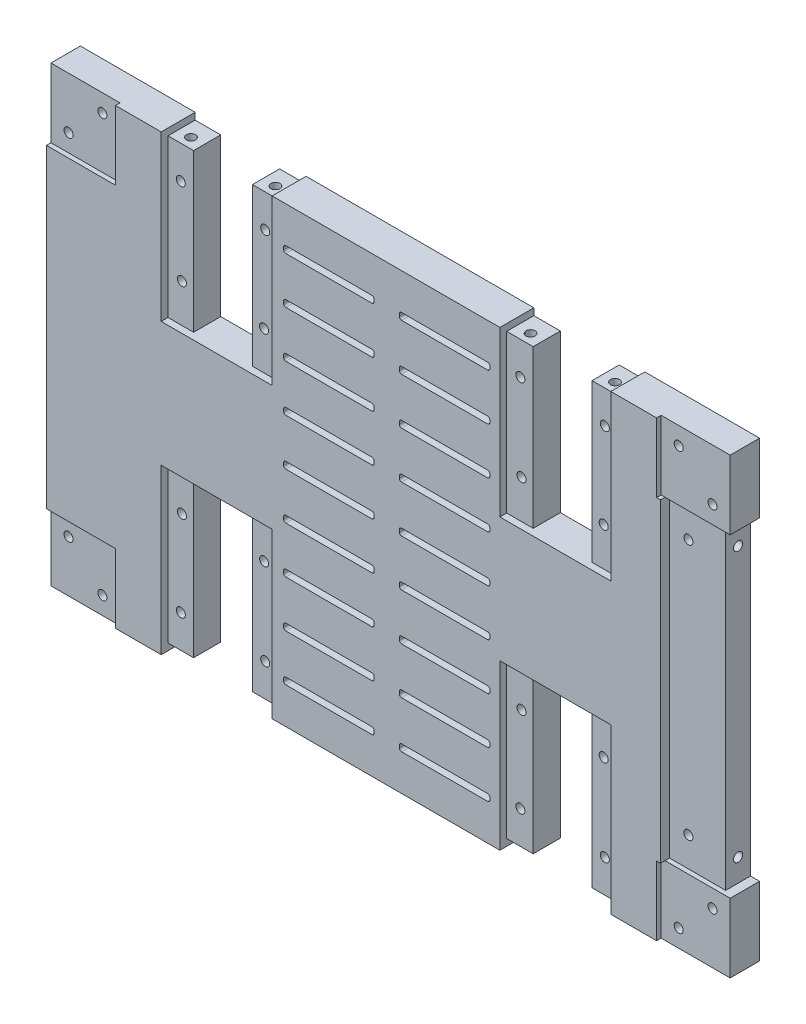
SolidWorks part; units mm, degrees
ref_plane "Alzado" through (0, 0, 0) normal (0, 0, 1) x (1, 0, 0)
ref_plane "Planta" through (0, 0, 0) normal (0, 1, 0) x (1, 0, 0)
ref_plane "Vista lateral" through (0, 0, 0) normal (1, 0, 0) x (0, 0, -1)
sketch "Croquis1" plane through (0, 0, 0) normal (0, 0, 1) x (1, 0, 0)
  line L1 (150, 100) -> (-150, 100)
  line L2 (150, 100) -> (150, -100)
  line L3 (150, -100) -> (-150, -100)
  line L4 (-150, 100) -> (-150, -100)
  line L5 (150, 100) -> (-150, -100) construction
  line L6 (150, -100) -> (-150, 100) construction
  point P0 (0, 0)
  dimension "D1" = 300
  dimension "D2" = 200
extrude "Saliente-Extruir1" add sketch "Croquis1" along normal blind 15
sketch "Croquis2" plane through (0, 0, 15) normal (0, 0, 1) x (1, 0, 0)
  line L0 (0, 0) -> (0, 100) construction
  line L1 (-150, 100) -> (-119.5, 100)
  line L2 (-150, 100) -> (-150, 69.5)
  line L3 (-150, 69.5) -> (-119.5, 69.5)
  line L4 (-119.5, 100) -> (-119.5, 69.5)
  line L5 (150, 100) -> (-150, 100) construction
  line L6 (0, 0) -> (150, 0) construction
  line L7 (150, -100) -> (150, 100) construction
  line L8 (150, 69.5) -> (119.5, 69.5)
  line L9 (119.5, 100) -> (119.5, 69.5)
  line L10 (150, 100) -> (119.5, 100)
  line L11 (150, 100) -> (150, 69.5)
  line L12 (150, -100) -> (150, -69.5)
  line L13 (150, -100) -> (119.5, -100)
  line L14 (119.5, -100) -> (119.5, -69.5)
  line L15 (150, -69.5) -> (119.5, -69.5)
  line L16 (-150, -69.5) -> (-119.5, -69.5)
  line L17 (-119.5, -100) -> (-119.5, -69.5)
  line L18 (-150, -100) -> (-119.5, -100)
  line L19 (-150, -100) -> (-150, -69.5)
  dimension "D1" = 30.5
extrude "Huecos columna" cut sketch "Croquis2" against normal blind 2
sketch "Croquis3" plane through (0, 0, 15) normal (0, 0, 1) x (1, 0, 0)
  line L0 (-119.5, -100) -> (119.5, -100) construction
  line L2 (-88, -97) -> (-88, -27.5)
  line L3 (-88, -27.5) -> (-62, -27.5)
  line L4 (-62, -97) -> (-62, -27.5)
  line L5 (0, 0) -> (0, -100) construction
  line L6 (0, 0) -> (-150, 0) construction
  line L7 (-150, 69.5) -> (-150, -69.5) construction
  line L8 (-88, -58.2044) -> (-150, -58.2044) construction
  line L9 (-62, -60.8904) -> (0, -60.8904) construction
  line L10 (88, -27.5) -> (62, -27.5)
  line L11 (62, -97) -> (62, -27.5)
  line L13 (88, -97) -> (88, -27.5)
  line L14 (88, 97) -> (88, 27.5)
  line L16 (62, 97) -> (62, 27.5)
  line L17 (88, 27.5) -> (62, 27.5)
  line L18 (-88, 27.5) -> (-62, 27.5)
  line L19 (-62, 97) -> (-62, 27.5)
  line L21 (-88, 97) -> (-88, 27.5)
  line L22 (-99.2954, -100) -> (-50.2954, -100)
  line L24 (-99.2954, -100) -> (-99.2954, -97)
  line L25 (-99.2954, -97) -> (-88, -97)
  line L26 (-50.2954, -100) -> (-50.2954, -97)
  line L27 (99.2954, -100) -> (50.2954, -100)
  line L28 (50.2954, -100) -> (50.2954, -97)
  line L29 (99.2954, -97) -> (88, -97)
  line L30 (99.2954, -100) -> (99.2954, -97)
  line L31 (99.2954, 100) -> (99.2954, 97)
  line L32 (99.2954, 97) -> (88, 97)
  line L33 (50.2954, 100) -> (50.2954, 97)
  line L34 (99.2954, 100) -> (50.2954, 100)
  line L35 (-99.2954, 100) -> (-50.2954, 100)
  line L36 (-50.2954, 100) -> (-50.2954, 97)
  line L37 (-99.2954, 97) -> (-88, 97)
  line L38 (-99.2954, 100) -> (-99.2954, 97)
  line L39 (-62, -97) -> (-50.2954, -97)
  line L40 (62, -97) -> (50.2954, -97)
  line L41 (62, 97) -> (50.2954, 97)
  line L42 (-62, 97) -> (-50.2954, 97)
  point P28 (-75, -100)
  point P36 (-74.7954, -100)
  dimension "D1" = 26
  dimension "D2" = 49
  dimension "D3" = 3
  dimension "D4" = 69.5
extrude "huecos  motor" cut sketch "Croquis3" against normal through all
sketch "Croquis4" plane through (0, -97, 0) normal (0, -1, 0) x (1, 0, 0)
  line L0 (-99.2954, 15) -> (-88, 0) construction
  line L1 (-88, 0) -> (-88, 15) construction
  line L2 (-88, 15) -> (-99.2954, 0) construction
  line L3 (0, 0) -> (0, 15) construction
  line L4 (-50.2954, 15) -> (50.2954, 15) construction
  line L5 (-75, 15) -> (-75, 0) construction
  line L6 (-62, 15) -> (-88, 15) construction
  line L7 (-62, 0) -> (-88, 0) construction
  circle A0 centre (-93.6477, 7.5) radius 2
  circle A1 centre (-56.3523, 7.5) radius 2
  circle A2 centre (56.3523, 7.5) radius 2
  circle A3 centre (93.6477, 7.5) radius 2
extrude "side_screws 1" cut sketch "Croquis4" against normal blind 15
sketch "Croquis5" plane through (0, 97, 0) normal (0, 1, 0) x (1, 0, 0)
  line L0 (-99.2954, 0) -> (-88, -15) construction
  line L1 (-88, -15) -> (-88, 0) construction
  line L2 (-88, 0) -> (-99.2954, -15) construction
  line L3 (-75, 0) -> (-75, -15) construction
  line L4 (-88, 0) -> (-62, 0) construction
  line L5 (-88, -15) -> (-62, -15) construction
  line L6 (0, 0) -> (0, -15) construction
  line L7 (50.2954, -15) -> (-50.2954, -15) construction
  circle A0 centre (-93.6477, -7.5) radius 2
  circle A1 centre (-56.3523, -7.5) radius 2
  circle A2 centre (56.3523, -7.5) radius 2
  circle A3 centre (93.6477, -7.5) radius 2
extrude "side screws 2" cut sketch "Croquis5" against normal blind 15
sketch "Croquis7" plane through (0, 0, 15) normal (0, 0, 1) x (1, 0, 0)
  line L0 (-150, -69.5) -> (-119.5, -100) construction
  line L1 (-150, -100) -> (-119.5, -69.5) construction
  line L2 (-150, 0) -> (0, 0) construction
  line L3 (-150, 69.5) -> (-150, -69.5) construction
  line L4 (0, 0) -> (0, -100) construction
  line L5 (-50.2954, -100) -> (50.2954, -100) construction
  line L6 (6.8759, 84) -> (44.8759, 84)
  line L7 (-44.236, 81) -> (-6.236, 81)
  line L8 (-45.236, 82) -> (-45.236, 83)
  line L9 (-44.236, 84) -> (-6.236, 84)
  line L10 (-5.236, 82) -> (-5.236, 83)
  line L11 (-45.236, 81) -> (-5.236, 84) construction
  line L12 (-45.236, 84) -> (-5.236, 81) construction
  line L13 (6.8759, 81) -> (44.8759, 81)
  line L14 (5.8759, 82) -> (5.8759, 83)
  line L15 (45.8759, 82) -> (45.8759, 83)
  line L16 (6.8759, 63.375) -> (44.8759, 63.375)
  line L17 (6.8759, 60.375) -> (44.8759, 60.375)
  line L18 (5.8759, 61.375) -> (5.8759, 62.375)
  line L19 (45.8759, 61.375) -> (45.8759, 62.375)
  line L20 (6.8759, 42.75) -> (44.8759, 42.75)
  line L21 (6.8759, 39.75) -> (44.8759, 39.75)
  line L22 (5.8759, 40.75) -> (5.8759, 41.75)
  line L23 (45.8759, 40.75) -> (45.8759, 41.75)
  line L24 (6.8759, 22.125) -> (44.8759, 22.125)
  line L25 (6.8759, 19.125) -> (44.8759, 19.125)
  line L26 (5.8759, 20.125) -> (5.8759, 21.125)
  line L27 (45.8759, 20.125) -> (45.8759, 21.125)
  line L28 (6.8759, 1.5) -> (44.8759, 1.5)
  line L29 (6.8759, -1.5) -> (44.8759, -1.5)
  line L30 (5.8759, -0.5) -> (5.8759, 0.5)
  line L31 (45.8759, -0.5) -> (45.8759, 0.5)
  line L32 (6.8759, -19.125) -> (44.8759, -19.125)
  line L33 (6.8759, -22.125) -> (44.8759, -22.125)
  line L34 (5.8759, -21.125) -> (5.8759, -20.125)
  line L35 (45.8759, -21.125) -> (45.8759, -20.125)
  line L36 (6.8759, -39.75) -> (44.8759, -39.75)
  line L37 (6.8759, -42.75) -> (44.8759, -42.75)
  line L38 (5.8759, -41.75) -> (5.8759, -40.75)
  line L39 (45.8759, -41.75) -> (45.8759, -40.75)
  line L40 (6.8759, -60.375) -> (44.8759, -60.375)
  line L41 (6.8759, -63.375) -> (44.8759, -63.375)
  line L42 (5.8759, -62.375) -> (5.8759, -61.375)
  line L43 (45.8759, -62.375) -> (45.8759, -61.375)
  line L44 (6.8759, -81) -> (44.8759, -81)
  line L45 (6.8759, -84) -> (44.8759, -84)
  line L46 (5.8759, -83) -> (5.8759, -82)
  line L47 (45.8759, -83) -> (45.8759, -82)
  line L48 (-44.236, 63.375) -> (-6.236, 63.375)
  line L49 (-44.236, 60.375) -> (-6.236, 60.375)
  line L50 (-45.236, 61.375) -> (-45.236, 62.375)
  line L51 (-5.236, 61.375) -> (-5.236, 62.375)
  line L52 (-44.236, 42.75) -> (-6.236, 42.75)
  line L53 (-44.236, 39.75) -> (-6.236, 39.75)
  line L54 (-45.236, 40.75) -> (-45.236, 41.75)
  line L55 (-5.236, 40.75) -> (-5.236, 41.75)
  line L56 (-44.236, 22.125) -> (-6.236, 22.125)
  line L57 (-44.236, 19.125) -> (-6.236, 19.125)
  line L58 (-45.236, 20.125) -> (-45.236, 21.125)
  line L59 (-5.236, 20.125) -> (-5.236, 21.125)
  line L60 (-44.236, 1.5) -> (-6.236, 1.5)
  line L61 (-44.236, -1.5) -> (-6.236, -1.5)
  line L62 (-45.236, -0.5) -> (-45.236, 0.5)
  line L63 (-5.236, -0.5) -> (-5.236, 0.5)
  line L64 (-44.236, -19.125) -> (-6.236, -19.125)
  line L65 (-44.236, -22.125) -> (-6.236, -22.125)
  line L66 (-45.236, -21.125) -> (-45.236, -20.125)
  line L67 (-5.236, -21.125) -> (-5.236, -20.125)
  line L68 (-44.236, -39.75) -> (-6.236, -39.75)
  line L69 (-44.236, -42.75) -> (-6.236, -42.75)
  line L70 (-45.236, -41.75) -> (-45.236, -40.75)
  line L71 (-5.236, -41.75) -> (-5.236, -40.75)
  line L72 (-44.236, -60.375) -> (-6.236, -60.375)
  line L73 (-44.236, -63.375) -> (-6.236, -63.375)
  line L74 (-45.236, -62.375) -> (-45.236, -61.375)
  line L75 (-5.236, -62.375) -> (-5.236, -61.375)
  line L76 (-44.236, -81) -> (-6.236, -81)
  line L77 (-44.236, -84) -> (-6.236, -84)
  line L78 (-45.236, -83) -> (-45.236, -82)
  line L79 (-5.236, -83) -> (-5.236, -82)
  line L80 (39.4634, 84) -> (39.4634, 100) construction
  line L81 (50.2954, 100) -> (-50.2954, 100) construction
  line L82 (-93.6477, -97) -> (-93.6477, -82.5) construction
  line L83 (25.8759, -84) -> (25.8759, -100) construction
  line L84 (-45.236, 82.5) -> (-56.3523, 82.5) construction
  line L85 (-5.236, 82.8086) -> (5.8759, 82.5) construction
  line L87 (45.8759, 82.5) -> (62, 82.5) construction
  line L88 (62, 97) -> (62, 27.5) construction
  line L89 (-88, -97) -> (-99.2954, -97) construction
  line L90 (-75, -27.5) -> (-75, -100) construction
  line L91 (-62, -27.5) -> (-88, -27.5) construction
  line L92 (-56.3523, -97) -> (-56.3523, -82.5) construction
  line L93 (56.3523, -97) -> (56.3523, -82.5) construction
  line L94 (93.6477, -97) -> (93.6477, -82.5) construction
  line L95 (93.6477, 97) -> (93.6477, 82.5) construction
  line L96 (56.3523, 97) -> (56.3523, 82.5) construction
  line L97 (-56.3523, 97) -> (-56.3523, 82.5) construction
  line L98 (-93.6477, 97) -> (-93.6477, 82.5) construction
  circle A0 centre (-127.2782, -92.2218) radius 2
  circle A1 centre (-142.2218, -77.2782) radius 2
  circle A2 centre (-127.2782, 92.2218) radius 2
  circle A3 centre (-142.2218, 77.2782) radius 2
  circle A4 centre (127.2782, -92.2218) radius 2
  circle A5 centre (142.2218, -77.2782) radius 2
  circle A6 centre (127.2782, 92.2218) radius 2
  circle A7 centre (142.2218, 77.2782) radius 2
  arc A8 (-5.236, 82) -> (-6.236, 81) centre (-6.236, 82) cw
  arc A9 (-5.236, 83) -> (-6.236, 84) centre (-6.236, 83) ccw
  arc A10 (-44.236, 81) -> (-45.236, 82) centre (-44.236, 82) cw
  arc A11 (-45.236, 83) -> (-44.236, 84) centre (-44.236, 83) cw
  arc A12 (5.8759, 83) -> (6.8759, 84) centre (6.8759, 83) cw
  arc A13 (6.8759, 81) -> (5.8759, 82) centre (6.8759, 82) cw
  arc A14 (45.8759, 83) -> (44.8759, 84) centre (44.8759, 83) ccw
  arc A15 (45.8759, 82) -> (44.8759, 81) centre (44.8759, 82) cw
  arc A16 (5.8759, 62.375) -> (6.8759, 63.375) centre (6.8759, 62.375) cw
  arc A17 (6.8759, 60.375) -> (5.8759, 61.375) centre (6.8759, 61.375) cw
  arc A18 (45.8759, 62.375) -> (44.8759, 63.375) centre (44.8759, 62.375) ccw
  arc A19 (45.8759, 61.375) -> (44.8759, 60.375) centre (44.8759, 61.375) cw
  arc A20 (5.8759, 41.75) -> (6.8759, 42.75) centre (6.8759, 41.75) cw
  arc A21 (6.8759, 39.75) -> (5.8759, 40.75) centre (6.8759, 40.75) cw
  arc A22 (45.8759, 41.75) -> (44.8759, 42.75) centre (44.8759, 41.75) ccw
  arc A23 (45.8759, 40.75) -> (44.8759, 39.75) centre (44.8759, 40.75) cw
  arc A24 (5.8759, 21.125) -> (6.8759, 22.125) centre (6.8759, 21.125) cw
  arc A25 (6.8759, 19.125) -> (5.8759, 20.125) centre (6.8759, 20.125) cw
  arc A26 (45.8759, 21.125) -> (44.8759, 22.125) centre (44.8759, 21.125) ccw
  arc A27 (45.8759, 20.125) -> (44.8759, 19.125) centre (44.8759, 20.125) cw
  arc A28 (5.8759, 0.5) -> (6.8759, 1.5) centre (6.8759, 0.5) cw
  arc A29 (6.8759, -1.5) -> (5.8759, -0.5) centre (6.8759, -0.5) cw
  arc A30 (45.8759, 0.5) -> (44.8759, 1.5) centre (44.8759, 0.5) ccw
  arc A31 (45.8759, -0.5) -> (44.8759, -1.5) centre (44.8759, -0.5) cw
  arc A32 (5.8759, -20.125) -> (6.8759, -19.125) centre (6.8759, -20.125) cw
  arc A33 (6.8759, -22.125) -> (5.8759, -21.125) centre (6.8759, -21.125) cw
  arc A34 (45.8759, -20.125) -> (44.8759, -19.125) centre (44.8759, -20.125) ccw
  arc A35 (45.8759, -21.125) -> (44.8759, -22.125) centre (44.8759, -21.125) cw
  arc A36 (5.8759, -40.75) -> (6.8759, -39.75) centre (6.8759, -40.75) cw
  arc A37 (6.8759, -42.75) -> (5.8759, -41.75) centre (6.8759, -41.75) cw
  arc A38 (45.8759, -40.75) -> (44.8759, -39.75) centre (44.8759, -40.75) ccw
  arc A39 (45.8759, -41.75) -> (44.8759, -42.75) centre (44.8759, -41.75) cw
  arc A40 (5.8759, -61.375) -> (6.8759, -60.375) centre (6.8759, -61.375) cw
  arc A41 (6.8759, -63.375) -> (5.8759, -62.375) centre (6.8759, -62.375) cw
  arc A42 (45.8759, -61.375) -> (44.8759, -60.375) centre (44.8759, -61.375) ccw
  arc A43 (45.8759, -62.375) -> (44.8759, -63.375) centre (44.8759, -62.375) cw
  arc A44 (5.8759, -82) -> (6.8759, -81) centre (6.8759, -82) cw
  arc A45 (6.8759, -84) -> (5.8759, -83) centre (6.8759, -83) cw
  arc A46 (45.8759, -82) -> (44.8759, -81) centre (44.8759, -82) ccw
  arc A47 (45.8759, -83) -> (44.8759, -84) centre (44.8759, -83) cw
  arc A48 (-45.236, 62.375) -> (-44.236, 63.375) centre (-44.236, 62.375) cw
  arc A49 (-44.236, 60.375) -> (-45.236, 61.375) centre (-44.236, 61.375) cw
  arc A50 (-5.236, 62.375) -> (-6.236, 63.375) centre (-6.236, 62.375) ccw
  arc A51 (-5.236, 61.375) -> (-6.236, 60.375) centre (-6.236, 61.375) cw
  arc A52 (-45.236, 41.75) -> (-44.236, 42.75) centre (-44.236, 41.75) cw
  arc A53 (-44.236, 39.75) -> (-45.236, 40.75) centre (-44.236, 40.75) cw
  arc A54 (-5.236, 41.75) -> (-6.236, 42.75) centre (-6.236, 41.75) ccw
  arc A55 (-5.236, 40.75) -> (-6.236, 39.75) centre (-6.236, 40.75) cw
  arc A56 (-45.236, 21.125) -> (-44.236, 22.125) centre (-44.236, 21.125) cw
  arc A57 (-44.236, 19.125) -> (-45.236, 20.125) centre (-44.236, 20.125) cw
  arc A58 (-5.236, 21.125) -> (-6.236, 22.125) centre (-6.236, 21.125) ccw
  arc A59 (-5.236, 20.125) -> (-6.236, 19.125) centre (-6.236, 20.125) cw
  arc A60 (-45.236, 0.5) -> (-44.236, 1.5) centre (-44.236, 0.5) cw
  arc A61 (-44.236, -1.5) -> (-45.236, -0.5) centre (-44.236, -0.5) cw
  arc A62 (-5.236, 0.5) -> (-6.236, 1.5) centre (-6.236, 0.5) ccw
  arc A63 (-5.236, -0.5) -> (-6.236, -1.5) centre (-6.236, -0.5) cw
  arc A64 (-45.236, -20.125) -> (-44.236, -19.125) centre (-44.236, -20.125) cw
  arc A65 (-44.236, -22.125) -> (-45.236, -21.125) centre (-44.236, -21.125) cw
  arc A66 (-5.236, -20.125) -> (-6.236, -19.125) centre (-6.236, -20.125) ccw
  arc A67 (-5.236, -21.125) -> (-6.236, -22.125) centre (-6.236, -21.125) cw
  arc A68 (-45.236, -40.75) -> (-44.236, -39.75) centre (-44.236, -40.75) cw
  arc A69 (-44.236, -42.75) -> (-45.236, -41.75) centre (-44.236, -41.75) cw
  arc A70 (-5.236, -40.75) -> (-6.236, -39.75) centre (-6.236, -40.75) ccw
  arc A71 (-5.236, -41.75) -> (-6.236, -42.75) centre (-6.236, -41.75) cw
  arc A72 (-45.236, -61.375) -> (-44.236, -60.375) centre (-44.236, -61.375) cw
  arc A73 (-44.236, -63.375) -> (-45.236, -62.375) centre (-44.236, -62.375) cw
  arc A74 (-5.236, -61.375) -> (-6.236, -60.375) centre (-6.236, -61.375) ccw
  arc A75 (-5.236, -62.375) -> (-6.236, -63.375) centre (-6.236, -62.375) cw
  arc A76 (-45.236, -82) -> (-44.236, -81) centre (-44.236, -82) cw
  arc A77 (-44.236, -84) -> (-45.236, -83) centre (-44.236, -83) cw
  arc A78 (-5.236, -82) -> (-6.236, -81) centre (-6.236, -82) ccw
  arc A79 (-5.236, -83) -> (-6.236, -84) centre (-6.236, -83) cw
  circle A80 centre (-93.6477, -82.5) radius 2
  circle A81 centre (-93.1477, -44.5033) radius 2
  circle A82 centre (-56.3523, -82.5) radius 2
  circle A83 centre (-56.8523, -44.5033) radius 2
  circle A84 centre (56.8523, -44.5033) radius 2
  circle A85 centre (56.3523, -82.5) radius 2
  circle A86 centre (93.6477, -82.5) radius 2
  circle A87 centre (93.1477, -44.5033) radius 2
  circle A88 centre (93.6477, 82.5) radius 2
  circle A89 centre (93.1477, 44.5033) radius 2
  circle A90 centre (56.3523, 82.5) radius 2
  circle A91 centre (56.8523, 44.5033) radius 2
  circle A92 centre (-56.3523, 82.5) radius 2
  circle A93 centre (-56.8523, 44.5033) radius 2
  circle A94 centre (-93.6477, 82.5) radius 2
  circle A95 centre (-93.1477, 44.5033) radius 2
  point P32 (-25.236, 82.5)
  dimension "D1" = 11
  dimension "D4" = 1
  dimension "D8" = 38
  dimension "D2" = 3
  dimension "D3" = 40
  dimension "D7" = 14.5
  dimension "D5" = 2
  dimension "D6" = 9
extrude "screws and venti" cut sketch "Croquis7" against normal blind 15
sketch "Croquis9" plane through (0, 0, 15) normal (0, 0, 1) x (1, 0, 0)
  line L1 (-99.2954, -97) -> (-50.2954, -97)
  line L2 (-99.2954, -97) -> (-99.2954, -27.5)
  line L3 (-99.2954, -27.5) -> (-50.2954, -27.5)
  line L4 (-50.2954, -97) -> (-50.2954, -27.5)
  line L5 (-62, -27.5) -> (-88, -27.5) construction
  line L6 (0, 0) -> (-102.0652, 0) construction
  line L7 (0, 0) -> (0, -97) construction
  line L8 (99.2954, -27.5) -> (50.2954, -27.5)
  line L9 (50.2954, -97) -> (50.2954, -27.5)
  line L10 (99.2954, -97) -> (50.2954, -97)
  line L11 (99.2954, -97) -> (99.2954, -27.5)
  line L12 (99.2954, 97) -> (99.2954, 27.5)
  line L13 (99.2954, 97) -> (50.2954, 97)
  line L14 (50.2954, 97) -> (50.2954, 27.5)
  line L15 (99.2954, 27.5) -> (50.2954, 27.5)
  line L16 (-99.2954, 27.5) -> (-50.2954, 27.5)
  line L17 (-50.2954, 97) -> (-50.2954, 27.5)
  line L18 (-99.2954, 97) -> (-50.2954, 97)
  line L19 (-99.2954, 97) -> (-99.2954, 27.5)
extrude "Cortar-Extruir6" cut sketch "Croquis9" against normal blind 3
sketch "Croquis13" plane through (150, 0, 0) normal (1, 0, 0) x (0, 0, -1)
  line L0 (0, -100) -> (0, 100) construction
  line L1 (-15, 69.5) -> (0, 69.5)
  line L2 (-15, 69.5) -> (-15, -69.5)
  line L3 (-15, -69.5) -> (0, -69.5)
  line L4 (0, 69.5) -> (0, -69.5)
extrude "Cortar-Extruir9" cut sketch "Croquis13" against normal blind 4
sketch "Croquis14" plane through (0, 0, 15) normal (0, 0, 1) x (1, 0, 0)
  line L0 (146, -69.5) -> (119.5, -69.5) construction
  line L1 (146, 69.5) -> (121.22, 69.5)
  line L2 (146, 69.5) -> (146, -69.5)
  line L3 (146, -69.5) -> (121.22, -69.5)
  line L4 (121.22, 69.5) -> (121.22, -69.5)
  dimension "D1" = 24.78
extrude "Cortar-Extruir10" cut sketch "Croquis14" against normal blind 4
sketch "Croquis15" plane through (0, 0, 11) normal (0, 0, 1) x (1, 0, 0)
  line L0 (150, -69.5) -> (121.22, -69.5) construction
  line L5 (121.22, 69.5) -> (150, 69.5) construction
  line L6 (121.22, 69.5) -> (121.22, -69.5) construction
  line L7 (129.59, 56.5) -> (129.59, -56.5) construction
  circle A0 centre (129.59, 56.5) radius 2
  circle A1 centre (129.59, -56.5) radius 2
  dimension "D1" = 4
  dimension "D2" = 13
  dimension "D3" = 8.37
  dimension "D4" = 13
extrude "Cortar-Extruir11" cut sketch "Croquis15" against normal blind 4
sketch "Croquis16" plane through (146, 0, 0) normal (1, 0, 0) x (0, 0, -1)
  line L0 (0, -59.5) -> (-5.5, -59.5) construction
  line L1 (0, -69.5) -> (0, 69.5) construction
  line L2 (-5.5, -59.5) -> (-5.5, 59.5) construction
  line L3 (-5.5, 59.5) -> (-5.5, 69.5) construction
  line L6 (0, 69.5) -> (-13, 69.5) construction
  line L7 (-13, -69.5) -> (0, -69.5) construction
  circle A0 centre (-5.5, 59.5) radius 2
  circle A1 centre (-5.5, -59.5) radius 2
  dimension "D2" = 4
  dimension "D1" = 5.5
  dimension "D3" = 10
  dimension "D4" = 10
extrude "side screws - updown" cut sketch "Croquis16" against normal blind 10
